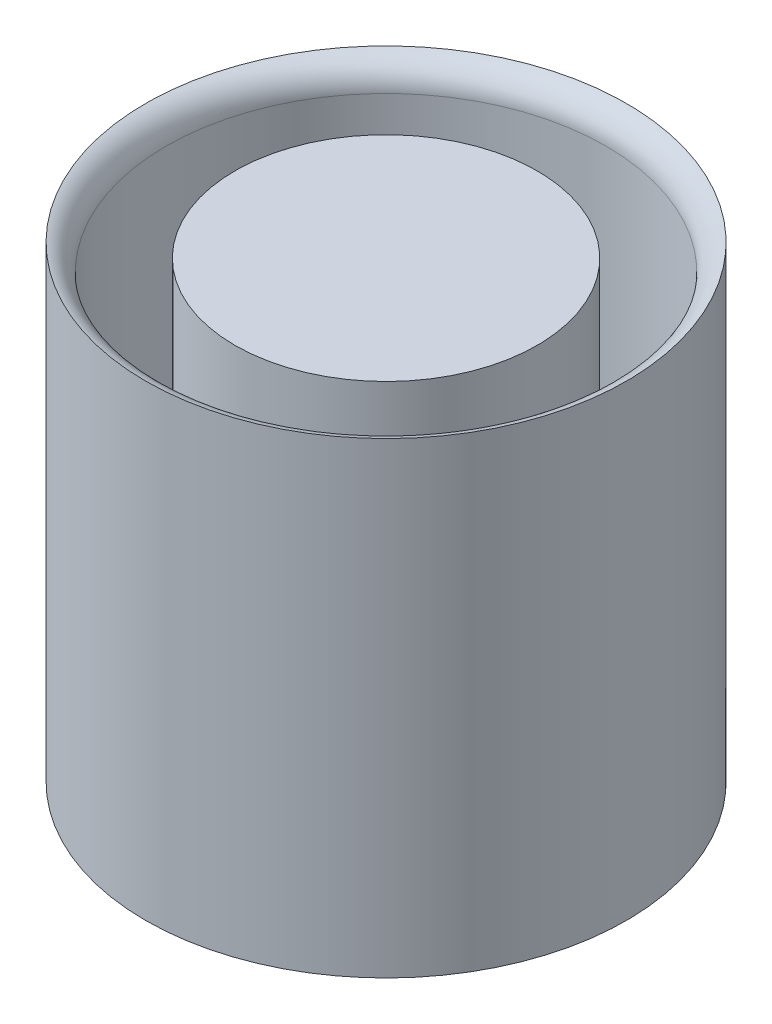
SolidWorks part; units mm, degrees
ref_plane "Alzado" through (0, 0, 0) normal (0, 0, 1) x (1, 0, 0)
ref_plane "Planta" through (0, 0, 0) normal (0, 1, 0) x (1, 0, 0)
ref_plane "Vista lateral" through (0, 0, 0) normal (1, 0, 0) x (0, 0, -1)
sketch "Sketch1" plane through (0, 0, 0) normal (0, 1, 0) x (1, 0, 0)
  circle A0 centre (0, 0) radius 17.5
  circle A1 centre (0, 0) radius 16
  dimension "D1" = 35
  dimension "D2" = 32
extrude "Boss-Extrude1" add sketch "Sketch1" along normal blind 34
sketch "Sketch2" plane through (0, 0, 0) normal (0, 1, 0) x (1, 0, 0)
  circle A0 centre (0, 0) radius 17.5
  dimension "D1" = 35
extrude "Boss-Extrude2" add sketch "Sketch2" along normal blind 3
fillet "Fillet1" radius 2 1 edges at (0, 34, 16)
ref_plane "Plane1" through (0, 3, 0) normal (0, 1, 0) x (1, 0, 0)
sketch "Sketch3" plane through (0, 3, 0) normal (0, 1, 0) x (1, 0, 0)
  circle A0 centre (0, 0) radius 11
  dimension "D1" = 22
extrude "Boss-Extrude3" add sketch "Sketch3" along normal blind 30
sketch "Sketch5" plane through (0, 33, 0) normal (0, 1, 0) x (1, 0, 0)
  line L0 (-1.0774, 1.3853) -> (1.0774, 1.3853)
  arc A0 (-1.0774, 1.3853) -> (1.0774, 1.3853) centre (0, 0) ccw
extrude "Cut-Extrude1" cut sketch "Sketch5" against normal blind 35
sketch "Sketch6" plane through (0, 33, 0) normal (0, 1, 0) x (1, 0, 0)
  line L0 (-1.3633, 1.3853) -> (1.2825, 1.3853) construction
  line L1 (-3.9815, 2.4079) -> (4.0095, 2.4079)
  line L2 (-3.9815, 2.4079) -> (-3.9815, -3.9849)
  line L3 (-3.9815, -3.9849) -> (4.0095, -3.9849)
  line L4 (4.0095, 2.4079) -> (4.0095, -3.9849)
  point P6 (-0.0404, 1.3853)
extrude "Boss-Extrude4" add sketch "Sketch6" against normal blind 24
